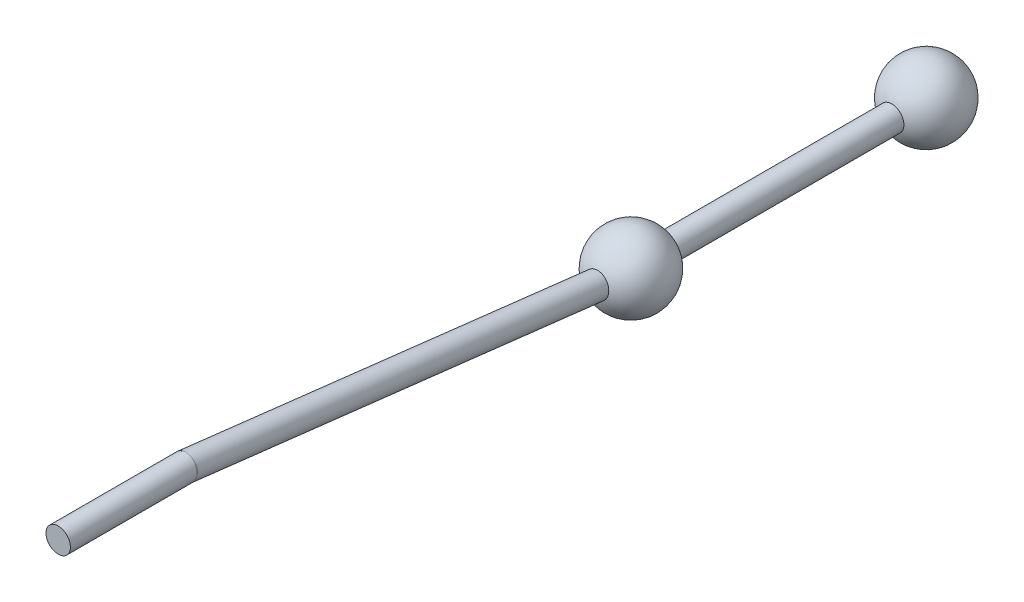
SolidWorks part; units mm, degrees
ref_plane "Front Plane" through (0, 0, 0) normal (0, 0, 1) x (1, 0, 0)
ref_plane "Top Plane" through (0, 0, 0) normal (0, 1, 0) x (1, 0, 0)
ref_plane "Right Plane" through (0, 0, 0) normal (1, 0, 0) x (0, 0, -1)
sketch "Sketch1" plane through (0, 0, 0) normal (1, 0, 0) x (0, 0, -1)
  line L0 (0, 0) -> (-1208, 0) construction
  line L1 (-1066.5786, 50) -> (-141.4214, 50)
  line L2 (-1358, 0) -> (150, 0) construction
  line L3 (-1358, 0) -> (150, 0)
  arc A0 (-1066.5786, 50) -> (-1358, 0) centre (-1208, 0) ccw
  arc A1 (150, 0) -> (-141.4214, 50) centre (0, 0) ccw
  dimension "D2" = 300
  dimension "D1" = 1208
  dimension "D3" = 50
revolve "Revolve1" add sketch "Sketch1" angle 360 about L3
sketch "Sketch2" plane through (0, 0, 0) normal (1, 0, 0) x (0, 0, -1)
  line L0 (-1245.5762, 0) -> (-2523.2662, 0) construction
  line L1 (-3550.6726, 209.3073) -> (-3031.5984, 209.3073)
  line L2 (-1245.5762, 0) -> (0, 0) construction
  line L3 (-3031.5984, 209.3073) -> (-1245.5762, 0)
  line L4 (-1206.418, 45.7532) -> (-3028.6786, 259.3073)
  line L5 (-3550.6726, 259.3073) -> (-3550.6726, 209.3073)
  line L6 (-3550.6726, 259.3073) -> (-3028.6786, 259.3073)
  line L8 (-1206.418, 45.7532) -> (-1245.5762, 0)
  line L9 (-3028.6786, 259.3073) -> (-3031.5984, 209.3073)
  dimension "D1" = 1277.69
  dimension "D2" = 50
  dimension "D3" = 50
revolve "Revolve5" add sketch "Sketch2" angle 360 about L1 region at (0, 234.3307, 3290.4049)
revolve "Revolve6" add sketch "Sketch2<11>" angle 360 about L3 region at (0, 128.6721, 2128.0326)
sketch "Sketch2<11>" plane through (0, 0, 0) normal (1, 0, 0) x (0, 0, -1) same geometry as "Sketch2"
